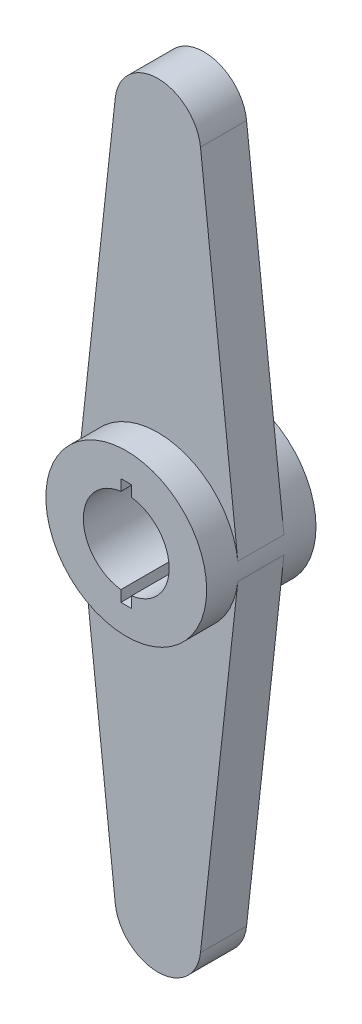
SolidWorks part; units mm, degrees
ref_plane "Ebene vorne" through (0, 0, 0) normal (0, 0, 1) x (1, 0, 0)
ref_plane "Ebene oben" through (0, 0, 0) normal (0, 1, 0) x (1, 0, 0)
ref_plane "Ebene rechts" through (0, 0, 0) normal (1, 0, 0) x (0, 0, -1)
sketch "Sketch1" plane through (0, 0, 0) normal (0, 0, 1) x (1, 0, 0)
  line L0 (-3.7276, 0.4089) -> (-1.9881, 16.2681)
  line L1 (0, 21.498) -> (0, -6.4772) construction
  line L2 (3.7276, 0.4089) -> (1.9881, 16.2681)
  line L3 (0, 0) -> (-15.4081, 0) construction
  line L4 (3.7276, -0.4089) -> (1.9881, -16.2681)
  line L5 (-3.7276, -0.4089) -> (-1.9881, -16.2681)
  line L7 (0.25, -2.5) -> (-0.25, -2.5)
  line L8 (0.25, -2.5) -> (0.25, 2.5)
  line L9 (0.25, 2.5) -> (-0.25, 2.5)
  line L10 (-0.25, -2.5) -> (-0.25, 2.5)
  line L11 (0.25, -2.5) -> (-0.25, 2.5) construction
  line L12 (0.25, 2.5) -> (-0.25, -2.5) construction
  circle A0 centre (0, 0) radius 3.75
  arc A2 (1.9881, -16.2681) -> (-1.9881, -16.2681) centre (0, -16.05) cw
  arc A3 (1.9881, 16.2681) -> (-1.9881, 16.2681) centre (0, 16.05) ccw
  circle A4 centre (0, 0) radius 2
  point P17 (0, 0)
  dimension "D1" = 7.5
  dimension "D2" = 0.5
  dimension "D4" = 4
  dimension "D3" = 5
extrude "Boss-Extrude1" add sketch "Sketch1" along normal mid plane 5.1 contours A0 A4 L10 L9 L8 L7 region at (0, 3.6439, 0)
sketch "Sketch2" plane through (0, 0, 0) normal (0, 0, 1) x (1, 0, 0)
  line L0 (-3.7276, -0.4089) -> (-1.9881, -16.2681) construction
  line L1 (3.7276, -0.4089) -> (1.9881, -16.2681) construction
  line L2 (3.7276, 0.4089) -> (1.9881, 16.2681) construction
  line L3 (-3.7276, 0.4089) -> (-1.9881, 16.2681) construction
  line L4 (-3.7276, -0.4089) -> (-1.9881, -16.2681)
  line L5 (3.7276, -0.4089) -> (1.9881, -16.2681)
  line L6 (3.7276, 0.4089) -> (1.9881, 16.2681)
  line L7 (-3.7276, 0.4089) -> (-1.9881, 16.2681)
  arc A0 (-1.9881, -16.2681) -> (1.9881, -16.2681) centre (0, -16.05) ccw construction
  circle A1 centre (0, 0) radius 3.75 construction
  arc A2 (1.9881, 16.2681) -> (-1.9881, 16.2681) centre (0, 16.05) ccw construction
  arc A3 (-1.9881, -16.2681) -> (1.9881, -16.2681) centre (0, -16.05) ccw
  circle A4 centre (0, 0) radius 3.75
  arc A5 (1.9881, 16.2681) -> (-1.9881, 16.2681) centre (0, 16.05) ccw
extrude "Boss-Extrude2" add sketch "Sketch2" along normal mid plane 2.15 contours L6 A5 L7 A4 | A4 L4 A3 L5 region at (0, -9.6133, 0) region at (0, 9.6133, 0)
